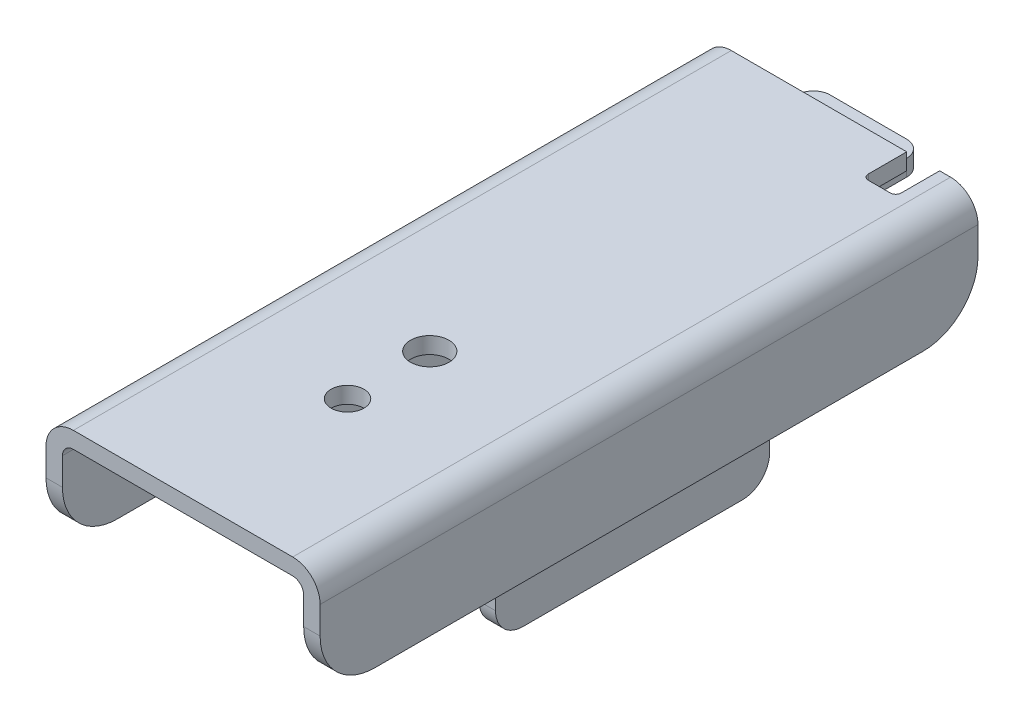
SolidWorks part; units mm, degrees
ref_plane "Front Plane" through (0, 0, 0) normal (0, 0, 1) x (1, 0, 0)
ref_plane "Top Plane" through (0, 0, 0) normal (0, 1, 0) x (1, 0, 0)
ref_plane "Right Plane" through (0, 0, 0) normal (1, 0, 0) x (0, 0, -1)
sketch "Sketch1" plane through (0, 0, 0) normal (0, 0, 1) x (1, 0, 0)
  line L16 (-48.5859, 38.4719) -> (-88.5859, 38.4719)
  line L17 (-93.5859, 33.4719) -> (-93.5859, 18.4719)
  line L18 (-93.5859, 18.4719) -> (-90.5859, 18.4719)
  line L19 (-90.5859, 18.4719) -> (-90.5859, 33.4719)
  line L20 (-88.5859, 35.4719) -> (-48.5859, 35.4719)
  line L21 (-46.5859, 33.4719) -> (-46.5859, 18.4719)
  line L22 (-46.5859, 18.4719) -> (-43.5859, 18.4719)
  line L23 (-43.5859, 18.4719) -> (-43.5859, 33.4719)
  arc A8 (-88.5859, 38.4719) -> (-93.5859, 33.4719) centre (-88.5859, 33.4719) ccw
  arc A9 (-88.5859, 35.4719) -> (-90.5859, 33.4719) centre (-88.5859, 33.4719) ccw
  arc A10 (-46.5859, 33.4719) -> (-48.5859, 35.4719) centre (-48.5859, 33.4719) ccw
  arc A11 (-43.5859, 33.4719) -> (-48.5859, 38.4719) centre (-48.5859, 33.4719) ccw
extrude "Boss-Extrude1" add sketch "Sketch1" along normal blind 120
fillet "Fillet1" radius 10 4 edges at (-92.0859, 18.4719, 0) (-45.0859, 18.4719, 0) (-92.0859, 18.4719, 120) (-45.0859, 18.4719, 120)
sketch "Sketch2" plane through (0, 18.4719, 0) normal (0, -1, 0) x (1, 0, 0)
  line L0 (-46.5859, 110) -> (-46.5859, 10) construction
  line L1 (-46.5859, 35) -> (-49.5859, 35)
  line L2 (-46.5859, 35) -> (-46.5859, 85)
  line L3 (-46.5859, 85) -> (-49.5859, 85)
  line L4 (-49.5859, 35) -> (-49.5859, 85)
  line L5 (-43.5859, 60) -> (-93.5859, 60) construction
  line L6 (-43.5859, 110) -> (-43.5859, 10) construction
  line L7 (-93.5859, 110) -> (-93.5859, 10) construction
  line L8 (-68.5859, 60) -> (-68.5859, 40.7332) construction
  line L9 (-87.5859, 35) -> (-87.5859, 85)
  line L10 (-90.5859, 85) -> (-87.5859, 85)
  line L11 (-90.5859, 35) -> (-90.5859, 85)
  line L12 (-90.5859, 35) -> (-87.5859, 35)
extrude "Boss-Extrude2" add sketch "Sketch2" against normal up to surface (17 mm away) and the other way blind 10 up to face at (-68.5859, 35.4719, 60)
sketch "Sketch3" plane through (0, 35.4719, 0) normal (0, -1, 0) x (1, 0, 0)
  line L0 (-68.5859, 0) -> (-68.5859, 20.5264) construction
  line L1 (-58.5859, 10) -> (-78.5859, 10)
  line L2 (-58.5859, 10) -> (-58.5859, -5)
  line L3 (-58.5859, -5) -> (-78.5859, -5)
  line L4 (-78.5859, 10) -> (-78.5859, -5)
  line L5 (-88.5859, 0) -> (-48.5859, 0) construction
  dimension "D1" = 10
  dimension "D2" = 20
  dimension "D3" = 15
  dimension "D4" = 10
extrude "Boss-Extrude3" add sketch "Sketch3" along normal blind 3
fillet "Fillet2" radius 5 4 edges at (-89.0859, 8.4719, 35) (-89.0859, 8.4719, 85) (-48.0859, 8.4719, 35) (-48.0859, 8.4719, 85)
chamfer "Chamfer1" distance 4 angle 45 1 edges at (-68.5859, 35.4719, 10)
fillet "Fillet3" radius 4 2 edges at (-68.5859, 35.4719, 14) (-68.5859, 32.4719, 11)
fillet "Fillet4" radius 3 2 edges at (-78.5859, 33.9719, -5) (-58.5859, 33.9719, -5)
sketch "Sketch4" plane through (0, 35.4719, 0) normal (0, -1, 0) x (1, 0, 0)
  line L0 (-46.5859, 35) -> (-46.5859, 10) construction
  line L1 (-46.5859, 20) -> (-90.5859, 20)
  line L2 (-46.5859, 20) -> (-46.5859, 23)
  line L3 (-46.5859, 23) -> (-90.5859, 23)
  line L4 (-90.5859, 20) -> (-90.5859, 23)
  line L5 (-90.5859, 35) -> (-90.5859, 10) construction
  line L6 (-46.5859, 110) -> (-46.5859, 85) construction
  line L7 (-46.5859, 100) -> (-90.5859, 100)
  line L8 (-46.5859, 100) -> (-46.5859, 97)
  line L9 (-46.5859, 97) -> (-90.5859, 97)
  line L10 (-90.5859, 100) -> (-90.5859, 97)
  line L11 (-90.5859, 110) -> (-90.5859, 85) construction
  line L12 (-88.5859, 120) -> (-48.5859, 120) construction
  line L13 (-88.5859, 0) -> (-78.5859, 0) construction
  line L14 (-68.5859, 97) -> (-68.5859, 23) construction
  line L15 (-90.5859, 80) -> (-90.5859, 40) construction
  line L16 (-90.5859, 61.5) -> (-46.5859, 61.5)
  line L17 (-90.5859, 61.5) -> (-90.5859, 58.5)
  line L18 (-90.5859, 58.5) -> (-46.5859, 58.5)
  line L19 (-46.5859, 61.5) -> (-46.5859, 58.5)
  line L20 (-46.5859, 40) -> (-46.5859, 80) construction
  line L21 (-93.5859, 60) -> (-43.5859, 60) construction
  line L22 (-93.5859, 110) -> (-93.5859, 10) construction
  line L23 (-43.5859, 110) -> (-43.5859, 10) construction
  dimension "D1" = 3
  dimension "D2" = 20
  dimension "D3" = 3
  dimension "D4" = 20
  dimension "D5" = 3
  dimension "D6" = 1.5
extrude "Boss-Extrude4" add sketch "Sketch4" along normal blind 5
fillet "Fillet5" radius 3 4 edges at (-49.5859, 35.4719, 46.75) (-49.5859, 35.4719, 73.25) (-87.5859, 35.4719, 73.25) (-87.5859, 35.4719, 46.75)
sketch "Sketch7" plane through (0, 38.4719, 0) normal (0, 1, 0) x (1, 0, 0)
  circle A0 centre (-68.5859, -75) radius 3.5
extrude "Cut-Extrude3" cut sketch "Sketch7" against normal up to surface (3 mm away) up to face at (-68.5859, 35.4719, 8.9142)
sketch "Sketch8" plane through (0, 38.4719, 0) normal (0, 1, 0) x (1, 0, 0)
  line L0 (-48.5859, -120) -> (-88.5859, -120) construction
  circle A0 centre (-68.5859, -90) radius 3
  dimension "D1" = 30
extrude "Cut-Extrude7" cut sketch "Sketch8" against normal blind 12
sketch "Sketch9" plane through (0, 38.4719, 0) normal (0, 1, 0) x (1, 0, 0)
  line L0 (-48.5859, 0) -> (-88.5859, 0) construction
  line L1 (-56.5859, 0) -> (-50.5859, 0)
  line L2 (-56.5859, 0) -> (-56.5859, -7)
  line L3 (-55.5859, -8) -> (-51.5859, -8)
  line L4 (-50.5859, 0) -> (-50.5859, -7)
  arc A0 (-51.5859, -8) -> (-50.5859, -7) centre (-51.5859, -7) ccw
  arc A1 (-56.5859, -7) -> (-55.5859, -8) centre (-55.5859, -7) ccw
  dimension "D1" = 1
extrude "Cut-Extrude8" cut sketch "Sketch9" against normal blind 3
sketch "Sketch11" plane through (0, 35.4719, 0) normal (0, -1, 0) x (1, 0, 0)
  line L1 (-60.5859, 108) -> (-76.5859, 108)
  line L2 (-60.5859, 108) -> (-60.5859, 118)
  line L3 (-60.5859, 118) -> (-76.5859, 118)
  line L4 (-76.5859, 108) -> (-76.5859, 118)
extrude "Cut-Extrude9" cut sketch "Sketch11" against normal blind 2
